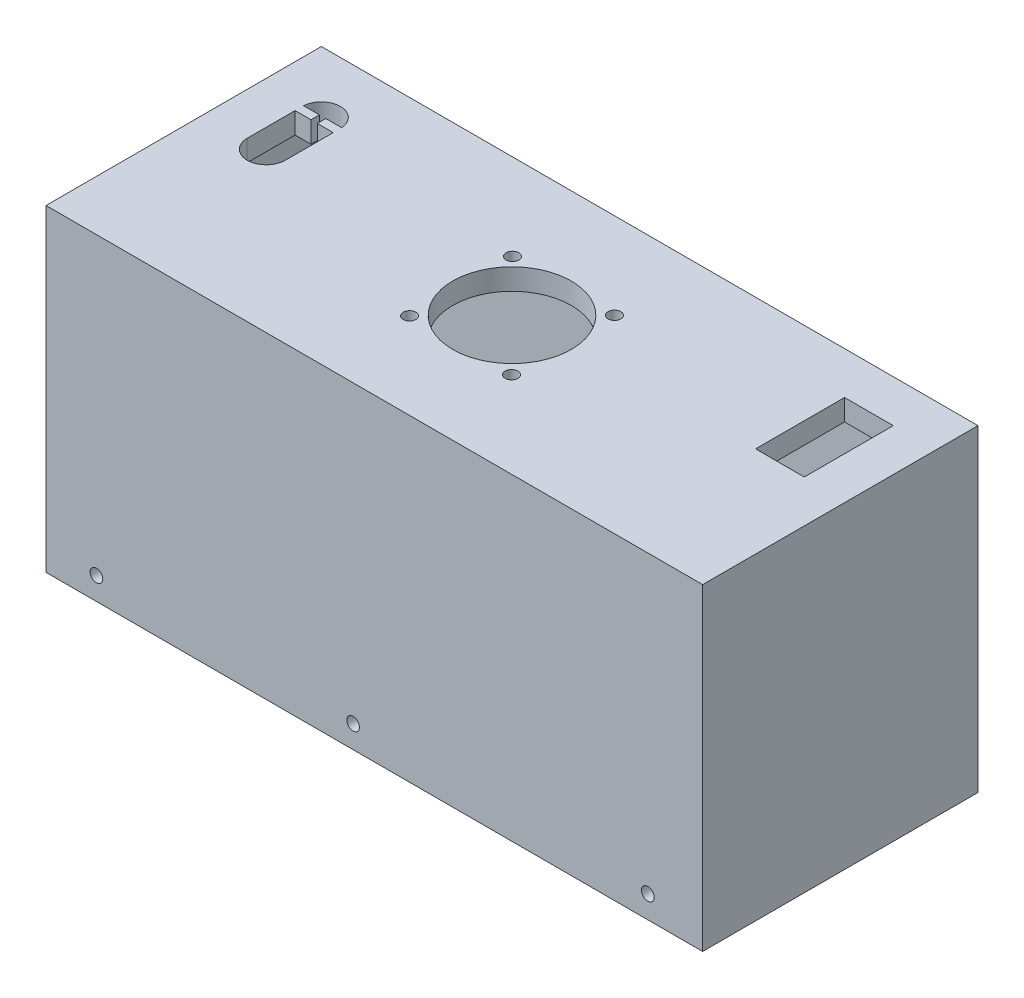
SolidWorks part; units mm, degrees
ref_plane "Front Plane" through (0, 0, 0) normal (0, 0, 1) x (1, 0, 0)
ref_plane "Top Plane" through (0, 0, 0) normal (0, 1, 0) x (1, 0, 0)
ref_plane "Right Plane" through (0, 0, 0) normal (1, 0, 0) x (0, 0, -1)
sketch "Sketch1" plane through (0, 0, 0) normal (0, 1, 0) x (1, 0, 0)
  line L5 (-140.9091, 6.5909) -> (14.0909, 6.5909)
  line L6 (-140.9091, 6.5909) -> (-140.9091, -58.4091)
  line L7 (-140.9091, -58.4091) -> (14.0909, -58.4091)
  line L8 (14.0909, 6.5909) -> (14.0909, -58.4091)
extrude "Boss-Extrude2" add sketch "Sketch1" along normal blind 75
sketch "Sketch2" plane through (0, 0, 0) normal (0, -1, 0) x (1, 0, 0)
  line L0 (-140.9091, 58.4091) -> (14.0909, 58.4091) construction
  line L1 (-135.9091, 53.4091) -> (9.0909, 53.4091)
  line L2 (-135.9091, 53.4091) -> (-135.9091, -1.5909)
  line L3 (-135.9091, -1.5909) -> (9.0909, -1.5909)
  line L4 (9.0909, 53.4091) -> (9.0909, -1.5909)
  line L5 (14.0909, -6.5909) -> (-140.9091, -6.5909) construction
  line L6 (14.0909, 58.4091) -> (14.0909, -6.5909) construction
  line L7 (-140.9091, -6.5909) -> (-140.9091, 58.4091) construction
  dimension "D1" = 5
  dimension "D2" = 5
  dimension "D3" = 5
  dimension "D4" = 5
extrude "Cut-Extrude1" cut sketch "Sketch2" against normal blind 70
sketch "Sketch3" plane through (0, 75, 0) normal (0, 1, 0) x (1, 0, 0)
  line L0 (-126.4091, -7.9091) -> (-126.4091, -20.9091) construction
  line L1 (-121.9091, -7.9091) -> (-121.9091, -20.9091)
  line L2 (-130.9091, -7.9091) -> (-130.9091, -20.9091)
  line L3 (-135.9091, -53.4091) -> (-135.9091, 1.5909) construction
  line L4 (-7.4091, -3.4091) -> (4.0909, -3.4091)
  line L5 (-7.4091, -3.4091) -> (-7.4091, -24.4091)
  line L6 (-7.4091, -24.4091) -> (4.0909, -24.4091)
  line L7 (-140.9091, -25.9091) -> (14.0909, -25.9091)
  line L8 (-140.9091, 6.5909) -> (-140.9091, -58.4091) construction
  line L9 (14.0909, -58.4091) -> (14.0909, 6.5909) construction
  line L10 (-63.4091, 6.5909) -> (-63.4091, -58.4091)
  line L11 (14.0909, 6.5909) -> (-140.9091, 6.5909) construction
  line L12 (-140.9091, -58.4091) -> (14.0909, -58.4091) construction
  line L13 (4.0909, -3.4091) -> (4.0909, -24.4091)
  line L14 (9.0909, -53.4091) -> (9.0909, 1.5909) construction
  line L15 (-135.9091, 1.5909) -> (9.0909, 1.5909) construction
  circle A0 centre (-63.4802, -25.8373) radius 14
  circle A1 centre (-75.4442, -13.7601) radius 1.5
  circle A2 centre (-51.3739, -13.7601) radius 1.5
  circle A3 centre (-51.3739, -38.0581) radius 1.5
  circle A4 centre (-75.4442, -38.0581) radius 1.5
  arc A5 (-121.9091, -7.9091) -> (-130.9091, -7.9091) centre (-126.4091, -7.9091) ccw
  arc A6 (-130.9091, -20.9091) -> (-121.9091, -20.9091) centre (-126.4091, -20.9091) ccw
  point P24 (-126.4091, -14.4091)
  dimension "D1" = 28
  dimension "D3" = 3
  dimension "D4" = 5
  dimension "D9" = 22
  dimension "D10" = 5
  dimension "D11" = 5
  dimension "D2" = 17
  dimension "D5" = 21
  dimension "D6" = 11.5
  dimension "D7" = 9
  dimension "D8" = 5
extrude "Cut-Extrude2" cut sketch "Sketch3" against normal blind 70 contours A1 | L10 A0 L7 | L7 A0 L10 | L10 A0 L7 | L7 A0 L10 | L13 L4 L5 L6 | A2 | A3 | A4 | A6 L1 A5 L2 region at (-1.6591, 75, 13.9091) region at (-69.3904, 75, 19.9275) region at (-69.3766, 75, 31.8247) region at (-57.4931, 75, 19.9412) region at (-57.5069, 75, 31.811) region at (-75.4442, 75, 13.7601)
sketch "Sketch5" plane through (0, 0, 58.4091) normal (0, 0, 1) x (1, 0, 0)
  circle A0 centre (-68.4121, 5.312) radius 1.5
  circle A1 centre (1.1564, 5.3239) radius 1.5
  circle A2 centre (-129.0082, 5.312) radius 1.5
extrude "Cut-Extrude3" cut sketch "Sketch5" against normal blind 73
sketch "Sketch6" plane through (0, 75, 0) normal (0, 1, 0) x (1, 0, 0)
  line L0 (-130.9091, -7.9091) -> (-130.9091, -20.9091) construction
  line L1 (-130.9091, -7.6091) -> (-127.1591, -7.6091)
  line L2 (-130.9091, -7.6091) -> (-130.9091, -9.6091)
  line L3 (-130.9091, -9.6091) -> (-127.1591, -9.6091)
  line L4 (-127.1591, -7.6091) -> (-127.1591, -9.6091)
  line L5 (-121.9091, -7.9091) -> (-121.9091, -20.9091) construction
  line L6 (-121.9091, -7.6091) -> (-125.6591, -7.6091)
  line L7 (-121.9091, -7.6091) -> (-121.9091, -9.6091)
  line L8 (-121.9091, -9.6091) -> (-125.6591, -9.6091)
  line L9 (-125.6591, -7.6091) -> (-125.6591, -9.6091)
  arc A0 (-121.9091, -7.9091) -> (-130.9091, -7.9091) centre (-126.4091, -7.9091) ccw construction
  dimension "D1" = 1.5
  dimension "D2" = 2
  dimension "D3" = 4.2
extrude "Boss-Extrude3" add sketch "Sketch6" against normal up to surface (5 mm away) up to face at (-126.4091, 70, 14.4091)
